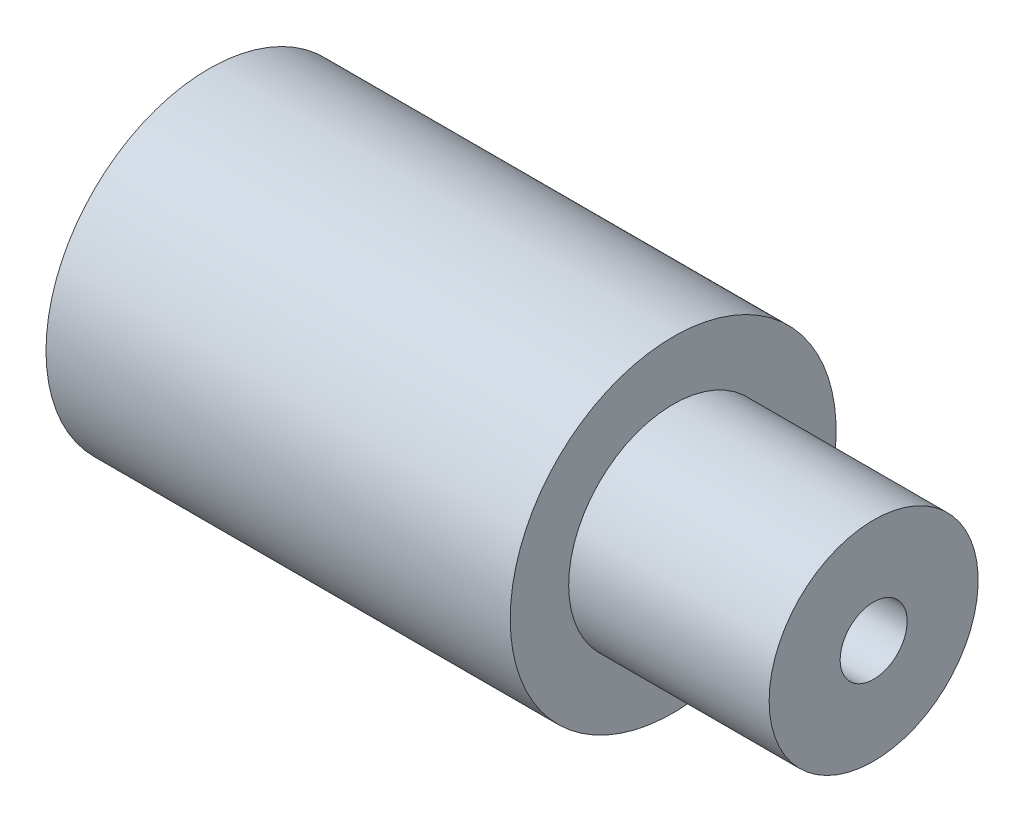
SolidWorks part; units mm, degrees
ref_plane "Front Plane" through (0, 0, 0) normal (0, 0, 1) x (1, 0, 0)
ref_plane "Top Plane" through (0, 0, 0) normal (0, 1, 0) x (1, 0, 0)
ref_plane "Right Plane" through (0, 0, 0) normal (1, 0, 0) x (0, 0, -1)
sketch "Conn_T2_ORB4_Bored Sketch" plane through (0, 0, 0) normal (0, 0, 1) x (1, 0, 0)
  line L0 (-1000, 0) -> (1000, 0) construction
  line L1 (9.5, 0) -> (9.5, 4.953)
  line L2 (9.5, 4.953) -> (0, 4.953)
  line L3 (0, 4.953) -> (0, 7.722)
  line L4 (0, 7.722) -> (-22, 7.722)
  line L5 (-22, 7.722) -> (-22, 0)
  line L6 (-22, 0) -> (9.5, 0)
revolve "Conn_T2_ORB4_Bored" add sketch "Conn_T2_ORB4_Bored Sketch" angle 360 about L0
ref_axis "Engine Axis" through (11.075, 0, 0) along (-1, 0, 0)
sketch "Socket Sketch" plane through (0, 0, 0) normal (0, 0, 1) x (1, 0, 0)
  line L0 (-1000, 0) -> (1000, 0) construction
  line L1 (-23, 0) -> (-23, 1.5875)
  line L2 (-23, 1.5875) -> (10.5, 1.5875)
  line L3 (10.5, 1.5875) -> (10.5, 0)
  line L4 (10.5, 0) -> (-23, 0)
revolve "Socket" cut sketch "Socket Sketch" angle 360 about L0
